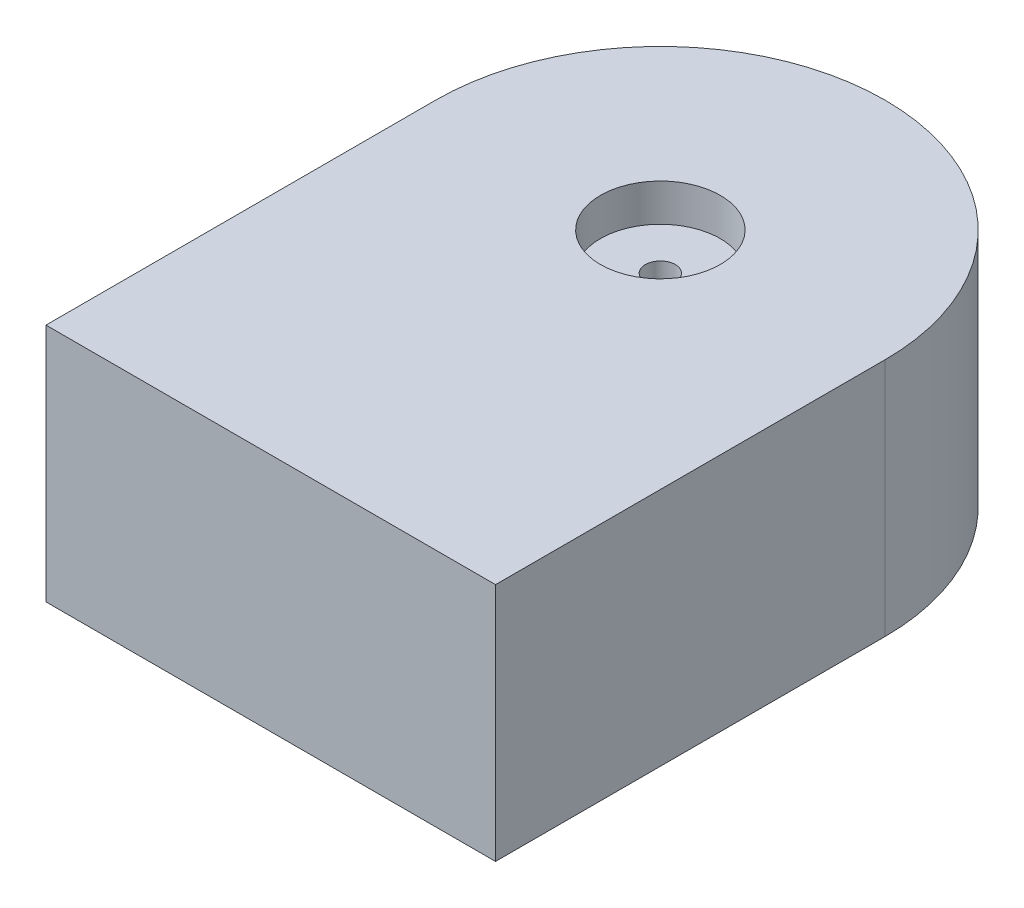
SolidWorks part; units mm, degrees
ref_plane "Plan de face" through (0, 0, 0) normal (0, 0, 1) x (1, 0, 0)
ref_plane "Plan de dessus" through (0, 0, 0) normal (0, 1, 0) x (1, 0, 0)
ref_plane "Plan de droite" through (0, 0, 0) normal (1, 0, 0) x (0, 0, -1)
sketch "Esquisse1" plane through (0, 0, 0) normal (0, 1, 0) x (1, 0, 0)
  line L1 (0, 0) -> (30, 0)
  line L2 (0, 0) -> (0, 41)
  line L3 (0, 41) -> (30, 41)
  line L4 (30, 0) -> (30, 41)
  dimension "D1" = 41
  dimension "D2" = 30
extrude "Extrusion1" add sketch "Esquisse1" along normal blind 16
fillet "Congé1" radius 15 2 edges at (30, 8, -41) (0, 8, -41)
sketch "Esquisse3" plane through (0, 16, 0) normal (0, 1, 0) x (1, 0, 0)
  circle A0 centre (15, 26) radius 4
  arc A1 (30, 26) -> (15, 41) centre (15, 26) ccw construction
  dimension "D1" = 8
extrude "Enlèv. mat.-Extru.1" cut sketch "Esquisse3" against normal blind 2.5
sketch "Esquisse4" plane through (0, 13.5, 0) normal (0, 1, 0) x (1, 0, 0)
  circle A0 centre (15, 26) radius 1
  circle A1 centre (15, 26) radius 4 construction
  dimension "D1" = 2
extrude "Enlèv. mat.-Extru.2" cut sketch "Esquisse4" against normal through all
